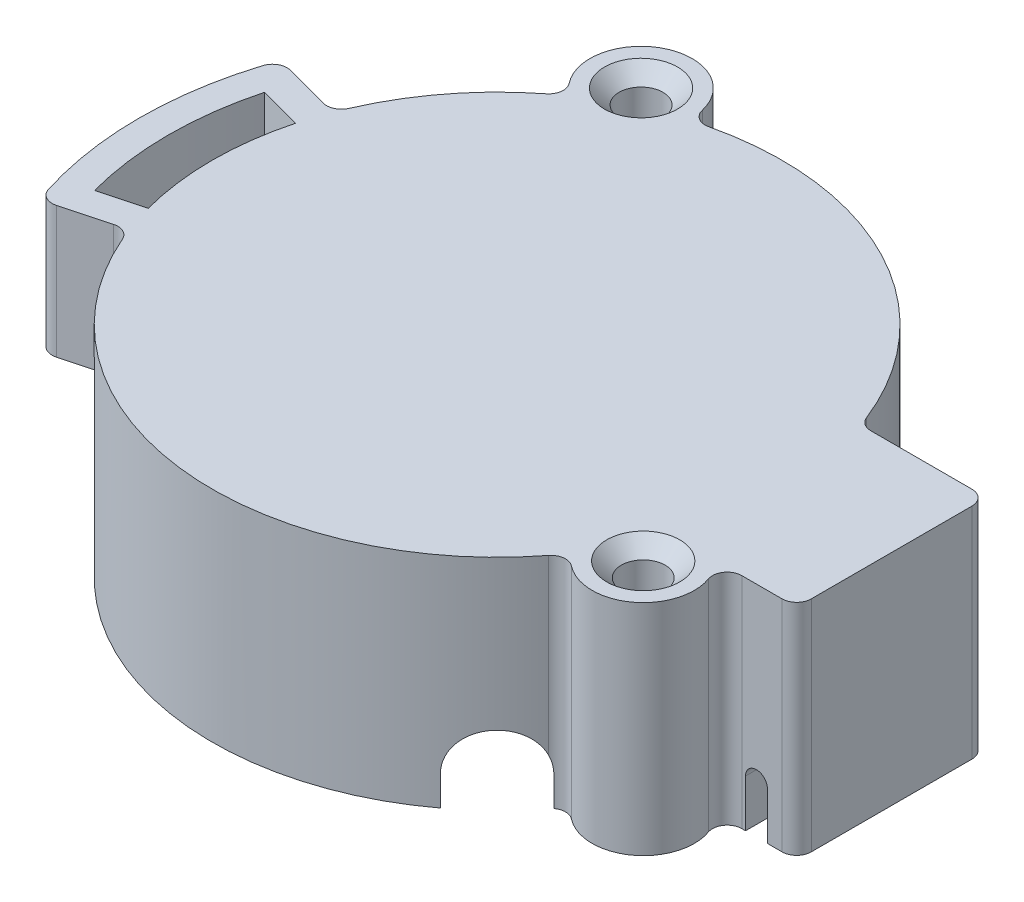
SolidWorks part; units mm, degrees
material "PET"
ref_plane "Front Plane" through (0, 0, 0) normal (0, 0, 1) x (1, 0, 0)
ref_plane "Top Plane" through (0, 0, 0) normal (0, 1, 0) x (1, 0, 0)
ref_plane "Right Plane" through (0, 0, 0) normal (1, 0, 0) x (0, 0, -1)
sketch "Sketch1" plane through (0, 0, 0) normal (0, 1, 0) x (1, 0, 0)
  line L0 (0, 0) -> (10.5413, 0) construction
  line L1 (16.9115, 4.5) -> (25, 4.5)
  line L2 (25, 4.5) -> (25, -4.5)
  line L3 (25, -4.5) -> (16.9115, -4.5)
  line L4 (18.3848, 6.5) -> (27, 6.5)
  line L5 (27, 6.5) -> (27, -6.5)
  line L6 (27, -6.5) -> (18.3848, -6.5)
  arc A0 (16.9115, 4.5) -> (16.9115, -4.5) centre (0, 0) ccw
  arc A1 (18.3848, 6.5) -> (18.3848, -6.5) centre (0, 0) ccw
  dimension "D1" = 35
  dimension "D2" = 39
  dimension "D3" = 9
  dimension "D4" = 13
  dimension "D5" = 25
  dimension "D6" = 2
extrude "Base" add sketch "Sketch1" against normal blind 13
sketch "Sketch2" plane through (0, 0, 0) normal (0, 1, 0) x (1, 0, 0)
  line L0 (27, -6.5) -> (27, 6.5) construction
  line L1 (18.3848, -6.5) -> (27, -6.5) construction
  line L2 (27, 6.5) -> (18.3848, 6.5) construction
  line L3 (27, -6.5) -> (27, 6.5)
  line L4 (18.3848, -6.5) -> (27, -6.5)
  line L5 (27, 6.5) -> (18.3848, 6.5)
  arc A0 (18.3848, 6.5) -> (18.3848, -6.5) centre (0, 0) ccw construction
  arc A1 (18.3848, 6.5) -> (18.3848, -6.5) centre (0, 0) ccw
extrude "Lid" add sketch "Sketch2" along normal blind 2
sketch "Sketch3" plane through (0, 0, 0) normal (0, -1, 0) x (1, 0, 0)
  line L0 (25, 3) -> (8.9115, 3)
  line L1 (7.9115, 2) -> (7.9115, -2)
  line L2 (8.9115, -3) -> (25, -3)
  line L3 (16.9115, 4.5) -> (9.9115, 4.5)
  line L4 (6.4115, 1) -> (6.4115, -1)
  line L5 (9.9115, -4.5) -> (16.9115, -4.5)
  line L6 (0, 0) -> (15.503, 0) construction
  line L7 (16.9115, 3) -> (8.9115, 3) construction
  line L8 (25, 4.5) -> (25, -4.5) construction
  line L9 (8.9115, -3) -> (16.9115, -3) construction
  line L10 (7.9115, 5.5) -> (16.6132, 5.5)
  line L12 (5.4115, 3) -> (5.4115, -3)
  line L14 (7.9115, -5.5) -> (16.6132, -5.5)
  arc A0 (8.9115, 3) -> (7.9115, 2) centre (7.9115, 3) ccw
  arc A1 (7.9115, -2) -> (8.9115, -3) centre (7.9115, -3) ccw
  arc A2 (9.9115, 4.5) -> (6.4115, 1) centre (7.9115, 3) ccw
  arc A3 (6.4115, -1) -> (9.9115, -4.5) centre (7.9115, -3) ccw
  arc A4 (16.9115, 4.5) -> (16.9115, -4.5) centre (0, 0) ccw construction
  arc A5 (16.9115, 4.5) -> (16.9115, -4.5) centre (0, 0) ccw construction
  dimension "D1" = 2
  dimension "D4" = 6
  dimension "D5" = 7.9115
  dimension "D3" = 1.5
extrude "Boss-Extrude1" add sketch "Sketch3" along normal blind 3
fillet "Fillet1" radius 1 4 edges at (8.9115, -1.5, -3) (7.9115, -1.5, -2) (7.9115, -1.5, 2) (8.9115, -1.5, 3)
sketch "Sketch4" plane through (0, -13, 0) normal (0, -1, 0) x (1, 0, 0)
  line L1 (9.7657, -20.7237) -> (-9.3255, -20.7237)
  line L2 (9.7657, -20.7237) -> (9.7657, -18.5)
  line L3 (9.7657, -18.5) -> (-9.3255, -18.5)
  line L4 (-9.3255, -20.7237) -> (-9.3255, -18.5)
  arc A0 (16.9115, 4.5) -> (16.9115, -4.5) centre (0, 0) ccw construction
  dimension "D1" = 1
extrude "Cut-Extrude1" [suppressed] cut sketch "Sketch4" against normal through all
ref_plane "Plane1" through (0, 0, 0) normal (0.7071, 0, 0.7071) x (0.7071, 0, -0.7071)
sketch "Sketch5" plane through (0, 0, 0) normal (0.7071, 0, 0.7071) x (0.7071, 0, -0.7071)
  line L0 (-2.75, -11) -> (-2.75, -14.3747)
  line L1 (-2.75, -14.3747) -> (2.75, -14.3747)
  line L2 (2.75, -14.3747) -> (2.75, -11)
  line L3 (-19.5, -13) -> (19.5, -13) construction
  circle A0 centre (0, -11) radius 2.75
  dimension "D1" = 5.5
  dimension "D2" = 2
extrude "Cut-Extrude2" cut sketch "Sketch5" against normal through all both and the other way through all contours A0 | A0 L0 L1 L2
sketch "Sketch6" plane through (0, 2, 0) normal (0, 1, 0) x (1, 0, 0)
  line L0 (0, 0) -> (19, -9) construction
  line L1 (0, 0) -> (-9.1019, 18.9514) construction
  circle A0 centre (19, -9) radius 1.5
  circle A1 centre (19, -9) radius 3.5
  circle A2 centre (-9.1019, 18.9514) radius 1.5
  circle A3 centre (-9.1019, 18.9514) radius 3.5
  dimension "D1" = 3
  dimension "D4" = 7
  dimension "D3" = 19
  dimension "D2" = 9
  dimension "D6" = 141
extrude "Boss-Extrude4" add sketch "Sketch6" along direction (0, 1, 0) on the side against the normal up to surface (15 mm away)
sketch "Sketch8" plane through (0, 2, 0) normal (0, 1, 0) x (1, 0, 0)
  line L8 (0, 0) -> (-6.024, 0) construction
  line L9 (0, 0) -> (-21.7333, 5.8234)
  line L11 (-21.7333, -5.8234) -> (0, 0)
  line L12 (7.7274, 0) -> (-23.0686, 8.2518)
  line L13 (-23.0686, -8.2518) -> (7.7274, 0)
  arc A1 (-21.7333, 5.8234) -> (-21.7333, -5.8234) centre (0, 0) ccw
  arc A2 (-11.0671, 16.0552) -> (16.1144, -10.9807) centre (0, 0) ccw construction
  arc A3 (-23.0686, 8.2518) -> (-23.0686, -8.2518) centre (0, 0) ccw
  dimension "D2" = 3
  dimension "D1" = 30
  dimension "D3" = 2
extrude "Boss-Extrude5" add sketch "Sketch8" against normal blind 9
fillet "Fillet2" radius 1 10 edges at (-18.2186, -2.5, -6.9522) (-23.0686, -2.5, -8.2518) (-23.0686, -2.5, 8.2518) (-18.2186, -2.5, 6.9522) (27, -5.5, 6.5) (27, -5.5, -6.5) (18.3848, -5.5, -6.5) (-11.0671, -5.5, -16.0552) (-5.6128, -5.5, -18.6747) (16.1144, -5.5, 10.9807)
sketch "Sketch9" plane through (0, 2, 0) normal (0, 1, 0) x (1, 0, 0)
  line L6 (21.4495, -6.5) -> (26, -6.5)
  line L7 (27, -5.5) -> (27, 5.5)
  line L8 (26, 6.5) -> (19.0788, 6.5)
  line L9 (-19.0707, 7.1805) -> (-22.1611, 8.0086)
  line L10 (-22.1611, -8.0086) -> (-19.0707, -7.1805)
  arc A19 (26, -6.5) -> (27, -5.5) centre (26, -5.5) ccw
  arc A20 (27, 5.5) -> (26, 6.5) centre (26, 5.5) ccw
  arc A21 (18.1481, 7.1341) -> (19.0788, 6.5) centre (19.0788, 7.5) ccw
  arc A22 (18.1481, 7.1341) -> (-4.4843, 18.9774) centre (0, 0) ccw
  arc A23 (-5.6893, 19.7285) -> (-4.4843, 18.9774) centre (-4.7142, 19.9506) ccw
  arc A24 (-5.6893, 19.7285) -> (-11.8418, 16.7736) centre (-9.1019, 18.9514) ccw
  arc A25 (-12.0088, 15.3635) -> (-11.8418, 16.7736) centre (-12.6247, 16.1514) ccw
  arc A26 (-12.0088, 15.3635) -> (-17.8942, 7.7491) centre (0, 0) ccw
  arc A27 (-19.0707, 7.1805) -> (-17.8942, 7.7491) centre (-18.8118, 8.1464) ccw
  arc A28 (-22.1611, 8.0086) -> (-23.3739, 7.3424) centre (-22.4199, 7.0427) ccw
  arc A29 (-23.3739, 7.3424) -> (-23.3739, -7.3424) centre (0, 0) ccw
  arc A30 (-23.3739, -7.3424) -> (-22.1611, -8.0086) centre (-22.4199, -7.0427) ccw
  arc A31 (-17.8942, -7.7491) -> (-19.0707, -7.1805) centre (-18.8118, -8.1464) ccw
  arc A32 (-17.8942, -7.7491) -> (15.4278, -11.9262) centre (0, 0) ccw
  arc A33 (16.837, -11.7516) -> (15.4278, -11.9262) centre (16.219, -12.5378) ccw
  arc A34 (16.837, -11.7516) -> (21.4495, -6.5) centre (19, -9) ccw
  circle A51 centre (19, -9) radius 3.5
  dimension "D1" = 0
extrude "Boss-Extrude6" [suppressed] add sketch "Sketch9" against normal up to surface (15 mm away) contours A51
sketch "Sketch10" plane through (0, 0, 6.5) normal (0, 0, 1) x (1, 0, 0)
  line L0 (25, -13) -> (25, -3) construction
  line L1 (23.5, -9.75) -> (23.5, -13.2303)
  line L2 (23.5, -13.2303) -> (25, -13.2303)
  line L3 (25, -13.2303) -> (25, -9.75)
  line L4 (21.4495, -13) -> (26, -13) construction
  circle A0 centre (24.25, -9.75) radius 0.75
  line M2 (21.4495, -13) -> (26, -13)
  dimension "D1" = 4
  dimension "D2" = 1.5
extrude "Cut-Extrude4" cut sketch "Sketch10" against normal blind 2 contours A0 L1 L3 M2 | A0
fillet "Fillet3" radius 1 1 edges at (21.4495, -5.5, 6.5)
chamfer "Chamfer1" distance 1 angle 45 2 edges at (-9.1019, 2, -17.4514) (19, 2, 10.5)
equation "\"D4@Sketch1\"=\"D3@Sketch1\"+4"
equation "\"D2@Sketch1\"=\"D1@Sketch1\"+4"
equation "\"D4@Sketch6\"=\"D1@Sketch6\"+4"
